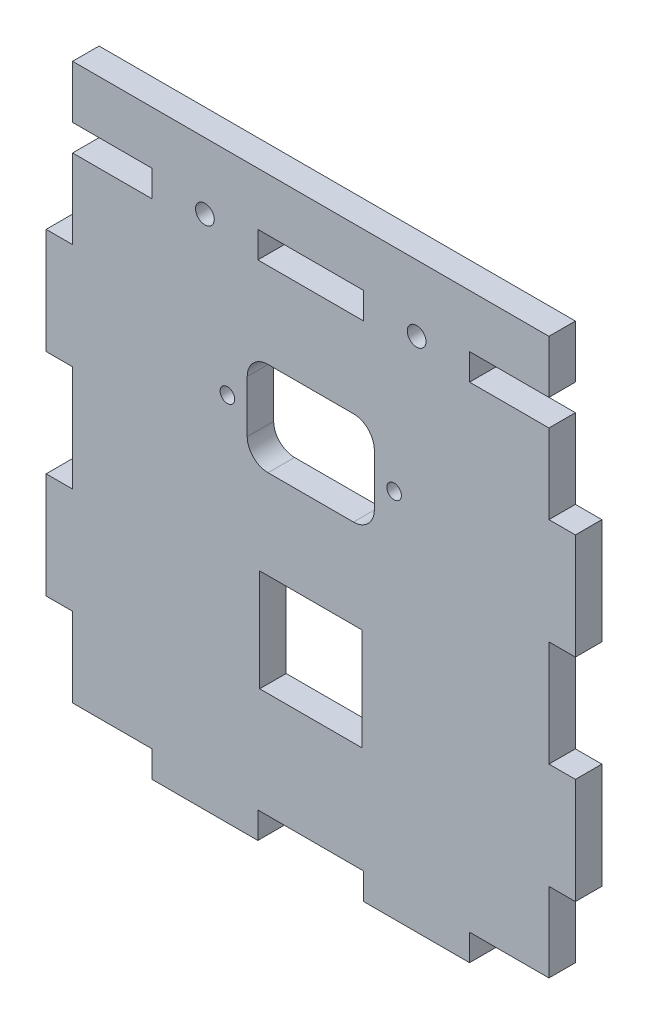
SolidWorks part; units mm, degrees
ref_plane "Front Plane" through (0, 0, 0) normal (0, 0, 1) x (1, 0, 0)
ref_plane "Top Plane" through (0, 0, 0) normal (0, 1, 0) x (1, 0, 0)
ref_plane "Right Plane" through (0, 0, 0) normal (1, 0, 0) x (0, 0, -1)
sketch "Sketch1" plane through (0, 0, 0) normal (0, 0, 1) x (1, 0, 0)
  line L1 (0, 0) -> (127, 0)
  line L2 (0, 0) -> (0, 139.7)
  line L3 (0, 139.7) -> (127, 139.7)
  line L4 (127, 0) -> (127, 139.7)
  dimension "D1" = 127
  dimension "D2" = 139.7
extrude "Boss-Extrude1" add sketch "Sketch1" along normal blind 6.35
sketch "Sketch5" plane through (0, 0, 6.35) normal (0, 0, 1) x (1, 0, 0)
  line L1 (0, 0) -> (6.35, 0)
  line L2 (0, 0) -> (0, 25.4)
  line L3 (0, 25.4) -> (6.35, 25.4)
  line L4 (6.35, 0) -> (6.35, 25.4)
  dimension "D1" = 25.4
  dimension "D2" = 6.35
extrude "Cut-Extrude4" cut sketch "Sketch5" against normal blind 6.35
sketch "Sketch6" plane through (0, 0, 6.35) normal (0, 0, 1) x (1, 0, 0)
  line L1 (0, 0) -> (25.4, 0)
  line L2 (0, 0) -> (0, 6.35)
  line L3 (0, 6.35) -> (25.4, 6.35)
  line L4 (25.4, 0) -> (25.4, 6.35)
  dimension "D1" = 6.35
  dimension "D2" = 25.4
extrude "Cut-Extrude5" cut sketch "Sketch6" against normal blind 6.35
pattern_linear "LPattern5" count 3 spacing 50.8 along (0, 1, 0) count 2 spacing 120.65 along (1, 0, 0) of "Cut-Extrude4"
pattern_linear "LPattern6" count 3 spacing 50.8 along (1, 0, 0) count 2 spacing 120.65 along (0, 1, 0) of "Cut-Extrude5"
sketch "Sketch7" plane through (0, 0, 6.35) normal (0, 0, 1) x (1, 0, 0)
  line L0 (127, 127) -> (101.6, 127) construction
  line L1 (6.35, 120.65) -> (0, 120.65)
  line L2 (6.35, 120.65) -> (6.35, 139.7)
  line L3 (6.35, 139.7) -> (0, 139.7)
  line L4 (0, 120.65) -> (0, 139.7)
  line L5 (127, 139.7) -> (120.65, 139.7)
  line L6 (127, 139.7) -> (127, 127)
  line L7 (127, 127) -> (120.65, 127)
  line L8 (120.65, 139.7) -> (120.65, 127)
  dimension "D1" = 6.35
  dimension "D2" = 19.05
  dimension "D3" = 6.35
extrude "Cut-Extrude6" cut sketch "Sketch7" against normal blind 6.35
hole_wizard "#8 Clearance Hole1" positions "Sketch10" profile "Sketch9" hole size "#8" standard "ANSI Inch"
sketch "Sketch10" plane through (0, 0, 6.35) normal (0, 0, 1) x (1, 0, 0)
  line L2 (25.4, 120.65) -> (25.4, 127) construction
  line L3 (76.2, 127) -> (50.8, 127) construction
  line L4 (76.2, 120.65) -> (76.2, 127) construction
  point P0 (38.1, 123.825)
  point P2 (88.9, 123.825)
  point P10 (25.4, 123.825)
  dimension "D1" = 12.7
  dimension "D3" = 12.7
  dimension "D4" = 3.175
sketch "Sketch9" plane through (38.1, 123.825, 6.35) normal (1, 0, 0) x (0, -1, 0)
  line L0 (0, 0) -> (0, 11.5107)
  line L1 (0, 11.5107) -> (2.2479, 10.16)
  line L2 (2.2479, 10.16) -> (2.2479, 0)
  line L5 (2.2479, 0) -> (0, 0)
  line L10 (0, 11.5107) -> (-2.2479, 10.16) construction
  line L11 (0, -6.35) -> (0, 107.95) construction
  dimension "Hole Dia." = 4.4958
  dimension "Hole Depth" = 10.16
  dimension "Drill Angle" = 118
sketch "Sketch12" plane through (0, 0, 6.35) normal (0, 0, 1) x (1, 0, 0)
  line L1 (53.25, 100.15) -> (73.75, 100.15)
  line L2 (48.25, 95.15) -> (48.25, 82.65)
  line L3 (53.25, 77.65) -> (73.75, 77.65)
  line L4 (78.75, 95.15) -> (78.75, 82.65)
  line L5 (120.65, 139.7) -> (6.35, 139.7) construction
  line L6 (120.65, 139.7) -> (6.35, 139.7) construction
  circle A0 centre (43.5, 88.9) radius 1.75
  circle A1 centre (83.5, 88.9) radius 1.75
  arc A2 (48.25, 82.65) -> (53.25, 77.65) centre (53.25, 82.65) ccw
  arc A3 (73.75, 100.15) -> (78.75, 95.15) centre (73.75, 95.15) cw
  arc A4 (73.75, 77.65) -> (78.75, 82.65) centre (73.75, 82.65) ccw
  arc A5 (48.25, 95.15) -> (53.25, 100.15) centre (53.25, 95.15) cw
  point P8 (78.75, 88.9)
  point P9 (63.5, 100.15)
  point P18 (78.75, 100.15)
  point P21 (78.75, 77.65)
  point P24 (48.25, 100.15)
  point P25 (63.5, 139.7)
  dimension "D1" = 3.5
  dimension "D2" = 3.5
  dimension "D10" = 5
  dimension "D11" = 5
  dimension "D12" = 5
  dimension "D13" = 5
  dimension "D3" = 40
  dimension "D4" = 30.5
  dimension "D5" = 22.5
  dimension "D6" = 0
  dimension "D7" = 20
  dimension "D8" = 0
  dimension "D9" = 50.8
extrude "Cut-Extrude9" cut sketch "Sketch12" against normal blind 6.35
sketch "Sketch13" plane through (0, 0, 6.35) normal (0, 0, 1) x (1, 0, 0)
  line L1 (51.25, 56.25) -> (75.75, 56.25)
  line L2 (51.25, 56.25) -> (51.25, 31.75)
  line L3 (51.25, 31.75) -> (75.75, 31.75)
  line L4 (75.75, 56.25) -> (75.75, 31.75)
  line L6 (120.65, 139.7) -> (6.35, 139.7) construction
  line L7 (76.2, 6.35) -> (50.8, 6.35) construction
  point P4 (63.5, 56.25)
  point P7 (63.5, 139.7)
  dimension "D1" = 24.5
  dimension "D2" = 24.5
  dimension "D3" = 0
  dimension "D4" = 25.4
extrude "Cut-Extrude10" cut sketch "Sketch13" against normal blind 6.35
